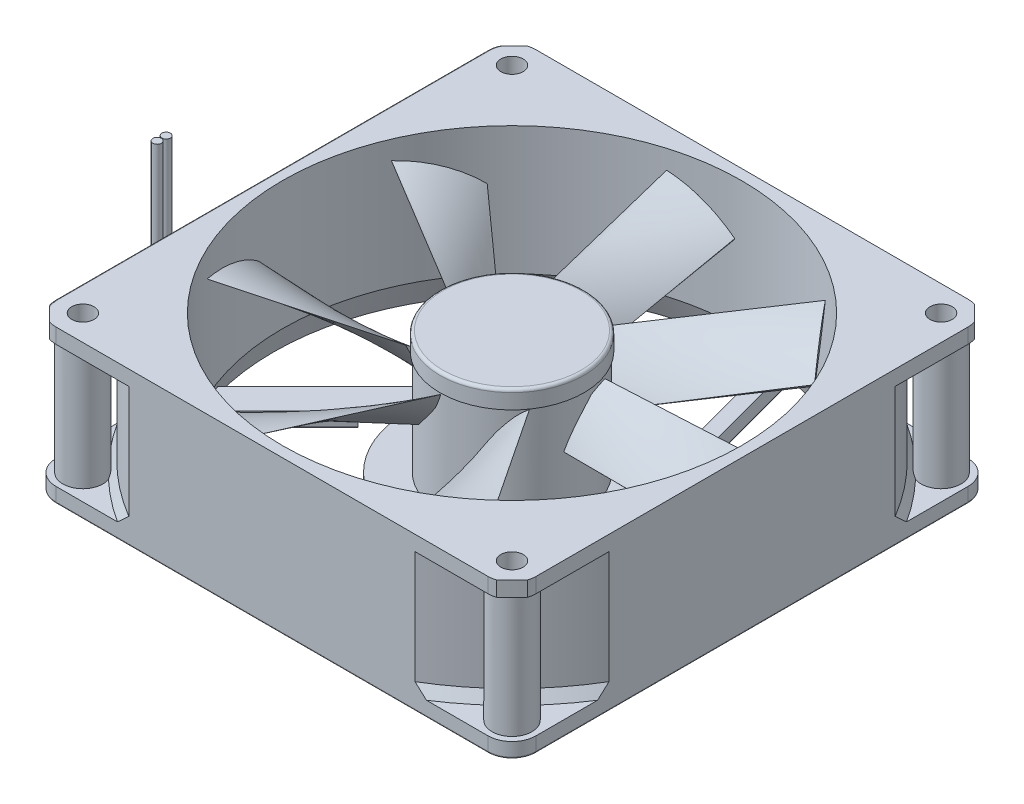
SolidWorks part; units mm, degrees
note: '?' marks a value the reader was unsure of.
ref_plane "Front" through (0, 0, 0) normal (0, 0, 1) x (1, 0, 0)
ref_plane "Top" through (0, 0, 0) normal (0, 1, 0) x (1, 0, 0)
ref_plane "Right" through (0, 0, 0) normal (1, 0, 0) x (0, 0, -1)
sketch "Sketch1" plane through (0, 0, 0) normal (0, 1, 0) x (1, 0, 0)
  line L1 (-40, 40) -> (40, 40)
  line L2 (-40, 40) -> (-40, -40)
  line L3 (-40, -40) -> (40, -40)
  line L4 (40, 40) -> (40, -40)
  dimension "Body Width Location" = 40
  dimension "Body Width" = 80
  dimension "Body Height Location" = 40
  dimension "Body Height" = 80
extrude "Main Body" add sketch "Sketch1" along normal blind 25.5
sketch "Sketch2" plane through (0, 0, 0) normal (0, -1, 0) x (1, 0, 0)
  circle A0 centre (0, 0) radius 38.25
  dimension "D1" = 76.5
extrude "Fan Hole Cut" cut sketch "Sketch2" against normal through all
chamfer "Fan Hole Front Chamfer" distance 1.5 angle 70 1 edges at (0, 0, -38.25)
sketch "Sketch3" plane through (0, 0, 0) normal (0, -1, 0) x (1, 0, 0)
  line L0 (-4.5293, 16.9037) -> (29.9451, 26.1411)
  line L1 (-25.8882, 0) -> (25.9703, 0) construction
  line L2 (4.8245, 16.8219) -> (31.6746, 24.0163)
  line L3 (0, 26.0113) -> (0, -25.7651) construction
  line L4 (16.9037, -4.5293) -> (7.6663, -39.0037)
  line L5 (12.1559, -12.589) -> (4.9615, -39.4391)
  line L6 (-12.3744, -12.3744) -> (-37.6114, 12.8626)
  line L7 (-17.4991, -0.1786) -> (-35.5204, 17.8427)
  arc A0 (-4.5293, 16.9037) -> (-17.4991, -0.1786) centre (0, 0) ccw
  arc A1 (-35.5204, 17.8427) -> (-37.6114, 12.8626) centre (0, 0) ccw
  arc A2 (16.9037, -4.5293) -> (4.8245, 16.8219) centre (0, 0) ccw
  arc A3 (-12.3744, -12.3744) -> (12.1559, -12.589) centre (0, 0) ccw
  arc A4 (31.6746, 24.0163) -> (29.9451, 26.1411) centre (0, 0) ccw
  arc A5 (4.9615, -39.4391) -> (7.6663, -39.0037) centre (0, 0) ccw
  circle A6 centre (0, 0) radius 39.75 construction
  dimension "D1" = 35
  dimension "D2" = 15
  dimension "D3" = 2.5
  dimension "D4" = 15
  dimension "D5" = 2.5
  dimension "D6" = 45
  dimension "D7" = 5
extrude "Fan Support" add sketch "Sketch3" against normal blind 2.5
sketch "Sketch4" plane through (0, 2.5, 0) normal (0, 1, 0) x (-1, 0, 0)
  circle A0 centre (0, 0) radius 11.75
  dimension "D1" = 23.5
extrude "PCB" add sketch "Sketch4" along normal blind 17.5
sketch "Sketch5" plane through (0, 20, 0) normal (0, 1, 0) x (-1, 0, 0)
  circle A0 centre (0, 0) radius 12
  dimension "D1" = 24
extrude "Fan Body" add sketch "Sketch5" along normal blind 3
fillet "Fan Hole Rear Fillet" [suppressed] radius 1
ref_plane "Plane1" through (0, 0, 0) normal (-0.7071, 0, -0.7071) x (-0.7071, 0, 0.7071)
sketch "Sketch6" plane through (0, 0, 0) normal (-0.7071, 0, -0.7071) x (-0.7071, 0, 0.7071)
  line L0 (-56.5685, 25.5) -> (-56.5685, 0) construction
  line L1 (-56.5685, 23) -> (-46.5685, 23)
  line L2 (-56.5685, 23) -> (-56.5685, 2.5)
  line L3 (-56.5685, 2.5) -> (-46.5685, 2.5)
  line L4 (-46.5685, 23) -> (-46.5685, 2.5)
  line L5 (-56.5685, 25.5) -> (0, 25.5) construction
  line L6 (26.25, 0) -> (-26.25, 0) construction
  line L7 (0, 25.5) -> (0, 0) construction
  dimension "D1" = 10
  dimension "D2" = 2.5
  dimension "D3" = 2.5
revolve "Outer Cut-Revolve1" cut sketch "Sketch6" angle 360 about L7
sketch "Sketch7" plane through (0, 0, 0) normal (0, 1, 0) x (1, 0, 0)
  circle A0 centre (35.75, 35.75) radius 3.33
  circle A1 centre (-35.75, 35.75) radius 3.33
  circle A2 centre (-35.75, -35.75) radius 3.33
  circle A3 centre (35.75, -35.75) radius 3.33
  dimension "D1" = 6.66
  dimension "D2" = 71.5
  dimension "D3" = 71.5
  dimension "D4" = 35.75
  dimension "D5" = 35.75
extrude "Mount Screw Extrude" add sketch "Sketch7" along normal up to surface (25.5 mm away) up to face at (0, 25.5, -38.25)
sketch "Sketch8" plane through (0, 0, 0) normal (0, 1, 0) x (1, 0, 0)
  circle A0 centre (35.75, 35.75) radius 1.85
  circle A1 centre (-35.75, 35.75) radius 1.85
  circle A2 centre (-35.75, -35.75) radius 1.85
  circle A3 centre (35.75, -35.75) radius 1.85
  dimension "D1" = 3.7
  dimension "D2" = 35.75
  dimension "D3" = 71.5
  dimension "D4" = 35.75
  dimension "D5" = 71.5
extrude "Mount Screw Holes" cut sketch "Sketch8" along normal up to surface (25.5 mm away) up to face at (0, 25.5, -38.25)
fillet "Corner Fillets" radius 4 8 edges at (-40, 24.25, 40) (-40, 1.25, 40) (40, 24.25, 40) (40, 1.25, 40) (40, 24.25, -40) (40, 1.25, -40) (-40, 1.25, -40) (-40, 24.25, -40)
ref_plane "Plane2" through (0, 0, -11) normal (0, 0, 1) x (1, 0, 0)
ref_plane "Plane3" through (0, 0, -36) normal (0, 0, 1) x (1, 0, 0)
sketch "Sketch9" plane through (0, 25.5, 0) normal (0, 1, 0) x (-1, 0, 0)
  line L0 (0, 0) -> (-35.75, 35.75) construction
  line L1 (-47.0416, 40.6423) -> (-49.5165, 43.1171)
  line L2 (-40.6423, 47.0416) -> (-43.1171, 49.5165)
  line L3 (-49.5165, 43.1171) -> (-51.6012, 41.0324)
  line L5 (-43.1171, 49.5165) -> (-41.0324, 51.6012)
  arc A0 (-51.6012, 41.0324) -> (-41.0324, 51.6012) centre (-35.75, 35.75) ccw
  arc A1 (-40.6423, 47.0416) -> (-47.0416, 40.6423) centre (0, 0) ccw
  dimension "D1" = 9.05
  dimension "D2" = 4.525
  dimension "D3" = 3.5
extrude "Cut-Extrude5" [suppressed] cut sketch "Sketch9" against normal up to surface (12.5 mm away)
pattern_circular "CirPattern1" [suppressed] count 4 over 360
sketch "Sketch10" plane through (0, 0, -11) normal (0, 0, 1) x (1, 0, 0)
  line L0 (-0.2648, 12.12) -> (0.1545, 12.3766)
  arc A0 (0.1545, 12.3766) -> (-6.03, 20.3498) centre (-16.0945, 6.1581) ccw
  arc A1 (-0.2648, 12.12) -> (-6.03, 20.3498) centre (30.55, 39.8409) cw
sketch "Sketch11" plane through (0, 0, -36) normal (0, 0, 1) x (1, 0, 0)
  line L0 (0.8831, 18.4239) -> (1.1168, 18.804)
  line L1 (12, 23) -> (-12, 23) construction
  arc A0 (1.1168, 18.804) -> (-10.2345, 23) centre (-11.2649, 2.7602) ccw
  arc A1 (0.8831, 18.4239) -> (-10.2345, 23) centre (14.3864, 67.0239) cw
loft "Fan Blade" add profiles "Sketch11", "Sketch10"
pattern_circular "Fan Blades CirPattern" count 7 over 360 about axis through (0, 25.5, 0) along (0, -1, 0) of "Fan Blade"
sketch "Sketch12" plane through (0, 25.5, 0) normal (0, 1, 0) x (-1, 0, 0)
  circle A0 centre (0, 0) radius 55
  dimension "D1" = 110
extrude "Fan Blade End Trim" cut sketch "Sketch12" against normal up to surface (23 mm away) thin up to face at (0.1595, 2.5, 0.516) thin type one direction reverse wall 0.5
sketch "Sketch13" plane through (0, 0, 0) normal (0, -1, 0) x (1, 0, 0)
  line L0 (-40, 20.9081) -> (-40, 16.6655)
  line L2 (-40, -36) -> (-40, 36) construction
  line L3 (0, 0) -> (-5.3553, 0) construction
  line L6 (-36.9043, 13.5697) -> (-11.6673, -11.6673)
  line L7 (-40, 16.6655) -> (-20.2132, -3.1213)
  line L8 (-18.0919, -4) -> (-5.3553, -4)
  line L9 (-18.2062, -0.8857) -> (-36.2275, 17.1356)
  line L10 (-23.0919, 4) -> (-40, 20.9081)
  line L11 (-5.3553, -4) -> (-5.3553, 4)
  line L12 (-23.0919, 4) -> (-5.3553, 4)
  arc A4 (-18.0919, -4) -> (-20.2132, -3.1213) centre (-18.0919, -1) cw
  dimension "D3" = 3
  dimension "D4" = 8
  dimension "D1" = 1
  dimension "D2" = 1
extrude "Wire Channel" cut sketch "Sketch13" against normal blind 2
sketch "Sketch17" plane through (0, 0, 0) normal (0, -1, 0) x (1, 0, 0)
  circle A0 centre (0, 0) radius 10
  dimension "D1" = 20
extrude "Label" add sketch "Sketch17" along normal blind 0.2
sketch "Sketch18" plane through (0, -0.2, 0) normal (0, -1, 0) x (1, 0, 0)
  line L0 (4.4381, 8.3885) -> (4.4381, -8.4128) construction
  line L1 (1.5844, 7.9717) -> (1.5844, -7.9318) construction
  text T0 "PAPST" font "Arial Black" height 2
  text T1 "TYP 512 F" font "Century Gothic" height 1
extrude "Label Text" add sketch "Sketch18" along normal blind 0.05
fillet "Front Edge Fillet" radius 0.25 19 edges at (15.2314, 0, 8.6171) (-12.5658, 0, 12.1799) (-0.1531, 0, -17.4993) (-40, 0, 28.4541) (-38.8284, 0, 38.8284) (-40, 0, -9.6673) (-38.8284, 0, -38.8284) (0, 0, -40) (38.8284, 0, -38.8284) (40, 0, 0) (38.8284, 0, 38.8284) (-31.5459, 0, 12.4541) (-28.599, 0, 10.9214) (12.285, 0, -21.7665) (12.7079, 0, 21.5224) (18.2495, 0, 20.4191) (-24.9929, 0, 0.2441) (8.5587, 0, -26.0141) (0, 0, 40)
fillet "Rear Edge Fillet" radius 0.25 3 edges at (-40, 25.5, 0) (-39.9518, 25.5, 36.6188) (-39.9518, 25.5, -36.6188)
fillet "Fan Body Fillet" radius 0.5 1 edges at (0, 23, 12)
chamfer "Outer Cut Chamfer" distance 1 angle 60 4 edges at (32.9289, 2.5, 32.9289) (32.9289, 2.5, -32.9289) (-32.9289, 2.5, 32.9289) (-32.9289, 2.5, -32.9289)
sketch3d "3DSketch1"
  line L0 (0, 2, 0) -> (-19.9706, 2, 0)
  line L1 (-22.0919, 2, 0.8787) -> (-37.3485, 2, 16.1353)
  line L2 (-38.4092, 2, 16.5747) -> (-40.09, 2, 16.5747)
  line L3 (-23.0919, 2, 4) -> (-40, 2, 20.9081) construction
  line L4 (-41.09, 3, 16.5747) -> (-41.09, 38.1234, 16.5747)
  line L5 (-23.0919, 0, 4) -> (-40, 0, 20.9081) construction
  arc A0 (-40.09, 2, 16.5747) -> (-41.09, 3, 16.5747) centre (-40.09, 3, 16.5747) ccw
  arc A1 (-19.9706, 2, 0) -> (-22.0919, 2, 0.8787) centre (-19.9706, 2, 3) ccw
  arc A2 (-37.3485, 2, 16.1353) -> (-38.4092, 2, 16.5747) centre (-38.4092, 2, 15.0747) ccw
  point P7 (-41.09, 2, 16.5747)
  point P8 (-40.09, 3, 15.5747)
  point P11 (-21.2132, 2, 0)
  point P12 (-19.9706, 5, 3)
  point P17 (-37.7879, 2, 16.5747)
  point P19 (-38.4092, 0.5, 15.0747)
  dimension "D1" = 1
  dimension "D2" = 1.5
  dimension "D3" = 2.5
sketch "Sketch19" plane through (0, 0, 0) normal (1, 0, 0) x (0, 0, -1)
  line L0 (-0.75, 2) -> (0.75, 2) construction
  line L1 (0.75, 2) -> (0, 2) construction
  circle A0 centre (-0.75, 1.29) radius 0.71
  circle A1 centre (0.75, 1.29) radius 0.71
  dimension "D1" = 1.42
  dimension "D2" = 1.5
sweep "Sweep1" add profiles "Sketch19" path "3DSketch1"
sketch "Sketch23" plane through (0, 38.1234, 0) normal (0, 1, 0) x (-1, 0, 0)
  line L0 (41.8, 15.8247) -> (41.8, 17.3247) construction
  point P4 (41.8, 16.5747)
other "CPoint1" parameters "Diameter"=1, "StubLength"=7
ref_axis "Axis1" through (-41.8, 48.1234, 16.5747) along (0, -1, 0)?
equation "\"Body Width Location@Sketch1\" = .5*\"Body Width@Sketch1\""
equation "\"Body Height Location@Sketch1\"=.5*\"Body Height@Sketch1\""
